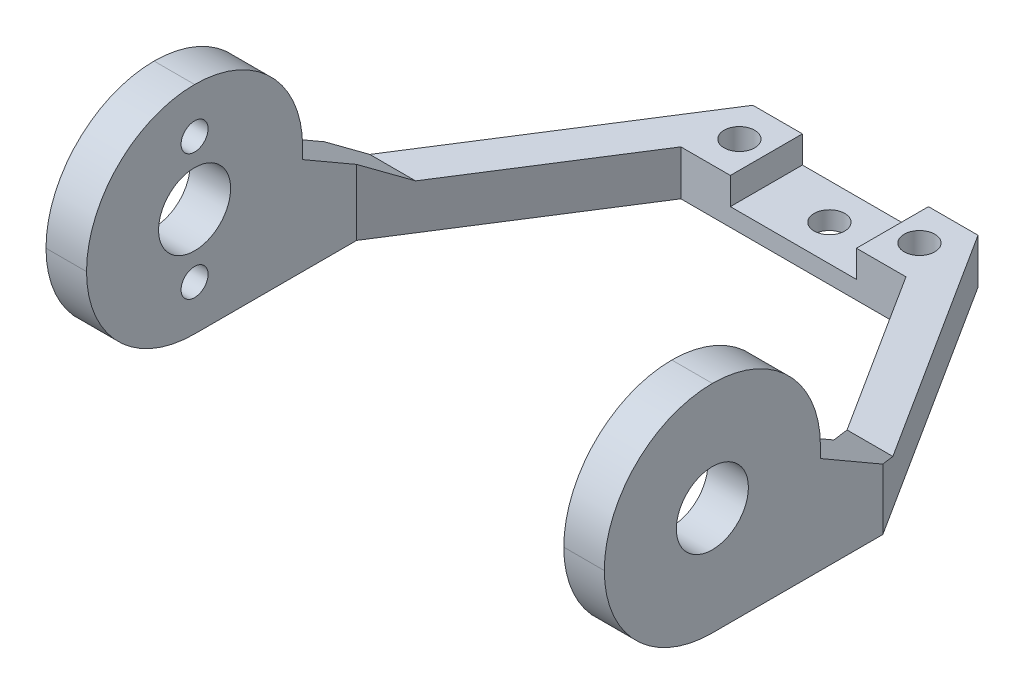
SolidWorks part; units mm, degrees
ref_plane "前视基准面" through (0, 0, 0) normal (0, 0, 1) x (1, 0, 0)
ref_plane "上视基准面" through (0, 0, 0) normal (0, 1, 0) x (1, 0, 0)
ref_plane "右视基准面" through (0, 0, 0) normal (1, 0, 0) x (0, 0, -1)
sketch "Sketch1" plane through (0, 0, 0) normal (0, 1, 0) x (1, 0, 0)
  line L0 (-31, 15.9286) -> (-31, -15)
  line L1 (-31, -15) -> (-26.5, -15)
  line L2 (-26.5, -15) -> (-26.5, 15)
  line L3 (-26.5, 15) -> (26.5, -15) construction
  line L4 (26.5, -15) -> (26.5, 15)
  line L5 (26.5, 15) -> (-26.5, -15) construction
  line L6 (26.5, -15) -> (31, -15)
  line L7 (31, -15) -> (31, 15.9286)
  line L8 (-31, 15.9286) -> (-12.5, 45)
  line L9 (-12.5, 45) -> (12.5, 45)
  line L10 (12.5, 45) -> (31, 15.9286)
  line L11 (-26.5, 15) -> (-12.5, 37)
  line L12 (-12.5, 37) -> (12.5, 37)
  line L13 (12.5, 37) -> (26.5, 15)
  line L14 (0, 45) -> (0, 37) construction
  line L15 (-26.5, -15) -> (26.5, -15) construction
  line L16 (0, 37) -> (0, 0) construction
  dimension "D4" = 8
  dimension "D1" = 53
  dimension "D2" = 30
  dimension "D3" = 4.5
  dimension "D6" = 25
  dimension "D7" = 60
extrude "Boss-Extrude1" add sketch "Sketch1" along normal blind 5
sketch "Sketch2" plane through (0, 5, 0) normal (0, 1, 0) x (1, 0, 0)
  line L0 (-31, 15.9286) -> (-31, -15) construction
  line L1 (-26.5, -15) -> (-26.5, 15) construction
  line L3 (-31, -15) -> (-26.5, -15) construction
  line L4 (-31, 9) -> (-31, -15)
  line L5 (-26.5, -15) -> (-26.5, 9)
  line L6 (-26.5, 9) -> (-31, 9)
  line L7 (-31, -15) -> (-26.5, -15)
  line L8 (26.5, 9) -> (31, 9)
  line L13 (26.5, 15) -> (26.5, -15) construction
  line L14 (31, -15) -> (31, 15.9286) construction
  line L15 (26.5, -15) -> (31, -15) construction
  line L18 (26.5, 9) -> (26.5, -15)
  line L19 (31, -15) -> (31, 9)
  line L20 (26.5, -15) -> (31, -15)
  dimension "D1" = 24
extrude "Boss-Extrude2" add sketch "Sketch2" along normal blind 19
sketch "Sketch5" plane through (0, 5, 0) normal (0, 1, 0) x (1, 0, 0)
  line L0 (12.5, 45) -> (-12.5, 45) construction
  line L1 (0, 45) -> (0, 37) construction
  line L2 (-12.5, 37) -> (12.5, 37) construction
  circle A0 centre (0, 41) radius 1.7
  point P0 (0, 45)
  dimension "D1" = 4
  dimension "D2" = 3.4
extrude "Cut-Extrude1" cut sketch "Sketch5" against normal up to next
sketch "Sketch6" plane through (0, 0, -45) normal (0, 0, -1) x (-1, 0, 0)
  line L0 (-12.5, 5) -> (12.5, 5) construction
  line L1 (-7, 2) -> (7, 2)
  line L2 (-7, 2) -> (-7, 5)
  line L3 (-7, 5) -> (7, 5)
  line L4 (7, 2) -> (7, 5)
  line L5 (-7, 2) -> (7, 5) construction
  line L6 (-7, 5) -> (7, 2) construction
  line L7 (0, 0) -> (0, 3.5) construction
  point P0 (0, 3.5)
  dimension "D1" = 3
  dimension "D2" = 14
extrude "Cut-Extrude2" cut sketch "Sketch6" against normal up to surface (8 mm away) up to face at (0, 2.5, -37)
sketch "Sketch7" plane through (-26.5, 0, 0) normal (1, 0, 0) x (0, 0, -1)
  line L0 (-3, 12) -> (-3, 24) construction
  line L1 (-15, 24) -> (9, 24) construction
  line L2 (-3, 12) -> (-15, 12) construction
  line L3 (-15, 24) -> (-15, 0) construction
  circle B0 centre (-3, 19) radius 1.5
  circle B1 centre (-3, 5) radius 1.5
sketch_block_instance "ArmHoles-1"
sketch_block "ArmHoles" parameters "D1"=4.0842
extrude "Cut-Extrude3" cut sketch "Sketch7" against normal up to next
sketch "Sketch8" plane through (-26.5, 0, 0) normal (1, 0, 0) x (0, 0, -1)
  line L0 (-3, 19) -> (-3, 5) construction
  circle A0 centre (-3, 12) radius 4
  dimension "D1" = 8
extrude "Cut-Extrude4" cut sketch "Sketch8" against normal through all both and the other way through all
fillet "Fillet1" radius 12 6 edges at (28.75, 0, 15) (-28.75, 0, 15) (-28.75, 24, -9) (28.75, 24, -9) (28.75, 24, 15) (-28.75, 24, 15)
chamfer "Chamfer2" distance 10 angle 30 2 edges at (28.75, 5, -9) first distance on face at (-18.9688, 5, -26.6741) first distance on face at (19.25, 5, -26.6161)
sketch "Sketch10" plane through (0, 5, 0) normal (0, 1, 0) x (1, 0, 0)
  line L0 (-7, 41) -> (-10, 41) construction
  line L1 (-7, 37) -> (-7, 45) construction
  circle A0 centre (-10, 41) radius 1.7
  dimension "D1" = 3.4
  dimension "D2" = 3
extrude "Cut-Extrude5" cut sketch "Sketch10" against normal up to next
mirror "Mirror1" about plane through (0, 0, 0) normal (1, 0, 0) of "Cut-Extrude5"
